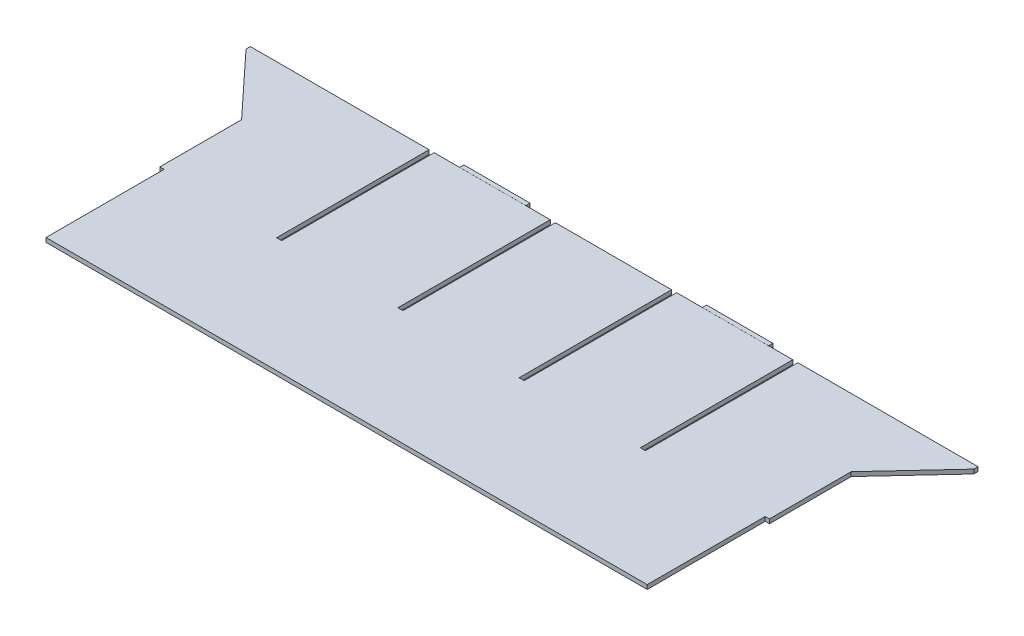
SolidWorks part; units mm, degrees
material "6061-T6 (SS)"
ref_plane "X-Y Datum" through (0, 0, 0) normal (0, 0, 1) x (1, 0, 0)
ref_plane "X-Z Datum" through (0, 0, 0) normal (0, 1, 0) x (1, 0, 0)
ref_plane "Y-Z Datum" through (0, 0, 0) normal (1, 0, 0) x (0, 0, -1)
sketch "Sketch1" plane through (0, 0, 0) normal (0, 0, 1) x (1, 0, 0)
  line L1 (-228.6115, -1.5875) -> (228.6115, -1.5875)
  line L2 (-228.6115, -1.5875) -> (-228.6115, 1.5875)
  line L3 (-228.6115, 1.5875) -> (228.6115, 1.5875)
  line L4 (228.6115, -1.5875) -> (228.6115, 1.5875)
  line L5 (-228.6115, -1.5875) -> (228.6115, 1.5875) construction
  line L6 (-228.6115, 1.5875) -> (228.6115, -1.5875) construction
  point P0 (0, 0)
  dimension "D1" = 3.175
  dimension "D2" = 457.223
extrude "Boss-Extrude1" add sketch "Sketch1" along normal blind 200.642
sketch "Sketch2" plane through (0, 1.5875, 0) normal (0, 1, 0) x (1, 0, 0)
  line L0 (228.6115, 0) -> (225.4365, 0)
  line L1 (228.6115, 0) -> (-228.6115, 0) construction
  line L2 (225.4365, 0) -> (137.8065, 0)
  line L3 (137.8065, 0) -> (133.986, 0)
  line L10 (133.986, 0) -> (137.8065, 0)
  line L11 (133.986, 0) -> (133.986, -114.3)
  line L12 (133.986, -114.3) -> (137.8065, -114.3)
  line L13 (137.8065, 0) -> (137.8065, -114.3)
  line M2 (228.6115, 0) -> (-228.6115, 0)
  dimension "D1" = 87.63
  dimension "D2" = 3.175
  dimension "D3" = 114.3
extrude "Cut-Extrude1" cut sketch "Sketch2" against normal through all contours L13 L11 L12 M2 region at (135.8963, 1.5875, 57.15)
pattern_linear "LPattern1" count 4 spacing 90.932 along (-1, 0, 0) of "Cut-Extrude1"
sketch "Sketch3" plane through (0, 0, 0) normal (0, 0, -1) x (-1, 0, 0)
  line L1 (-66.1907, 1.6167) -> (-115.8495, 1.6167)
  line L2 (-66.1907, 1.6167) -> (-66.1907, -1.5583)
  line L3 (-66.1907, -1.5583) -> (-115.8495, -1.5583)
  line L4 (-115.8495, 1.6167) -> (-115.8495, -1.5583)
  line L5 (66.1907, 1.6167) -> (115.8495, 1.6167)
  line L6 (66.1907, 1.6167) -> (66.1907, -1.5583)
  line L7 (66.1907, -1.5583) -> (115.8495, -1.5583)
  line L8 (115.8495, 1.6167) -> (115.8495, -1.5583)
sketch "Sketch4" plane through (0, -1.5875, 0) normal (0, -1, 0) x (1, 0, 0)
  line L0 (-228.6115, 0) -> (-272.8865, 0)
  line L2 (-228.6115, 200.642) -> (-228.6115, 0) construction
  line L3 (-228.6115, 50.8) -> (-228.6115, 0)
  line L4 (-272.8865, 0) -> (-272.8865, 3.175)
  line L5 (-272.8865, 3.175) -> (-228.6115, 50.8)
  dimension "D1" = 44.275
  dimension "D2" = 50.8
  dimension "D3" = 3.175
extrude "Boss-Extrude3" add sketch "Sketch4" against normal blind 3.175
mirror "Mirror1" about plane through (0, 0, 0) normal (1, 0, 0) of "Boss-Extrude3"
sketch "Sketch5" plane through (0, -1.5875, 0) normal (0, -1, 0) x (1, 0, 0)
  line L1 (-228.6115, 200.642) -> (-225.4365, 200.642)
  line L2 (-228.6115, 200.642) -> (-228.6115, 112.128)
  line L3 (-228.6115, 112.128) -> (-225.4365, 112.128)
  line L4 (-225.4365, 200.642) -> (-225.4365, 112.128)
  dimension "D1" = 3.175
  dimension "D2" = 88.514
extrude "Cut-Extrude2" cut sketch "Sketch5" against normal blind 3.175
mirror "Mirror2" about plane through (0, 0, 0) normal (1, 0, 0) of "Cut-Extrude2"
extrude "Boss-Extrude4" add sketch "Sketch3" along normal blind 3.175
